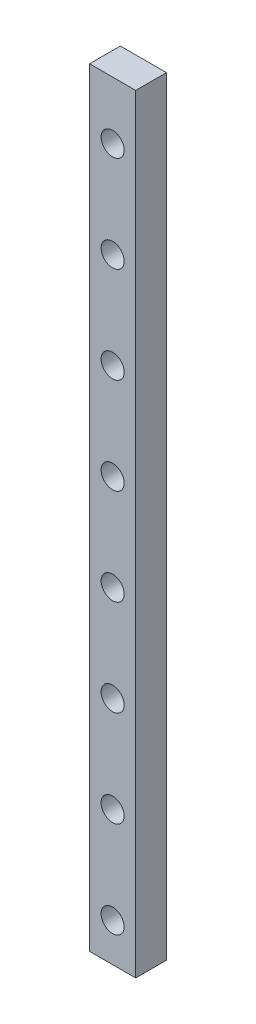
SolidWorks part; units mm, degrees
ref_plane "前视基准面" through (0, 0, 0) normal (0, 0, 1) x (1, 0, 0)
ref_plane "上视基准面" through (0, 0, 0) normal (0, 1, 0) x (1, 0, 0)
ref_plane "右视基准面" through (0, 0, 0) normal (1, 0, 0) x (0, 0, -1)
sketch "草图1" plane through (0, 0, 0) normal (0, 1, 0) x (1, 0, 0)
  line L1 (6, -4) -> (-6, -4)
  line L2 (6, -4) -> (6, 4)
  line L3 (6, 4) -> (-6, 4)
  line L4 (-6, -4) -> (-6, 4)
  line L5 (6, -4) -> (-6, 4) construction
  line L6 (6, 4) -> (-6, -4) construction
  point P0 (0, 0)
  dimension "D1" = 12
  dimension "D2" = 8
extrude "凸台-拉伸1" add sketch "草图1" along normal blind 200
sketch "草图2" plane through (0, 0, 4) normal (0, 0, 1) x (1, 0, 0)
  line L0 (0, -1000) -> (0, 49000) construction
  line L1 (-6, 0) -> (6, 0) construction
  circle A0 centre (0, 10) radius 3
  dimension "D1" = 6
  dimension "D2" = 10
extrude "切除-拉伸1" cut sketch "草图2" against normal blind 4.5
sketch "草图3" plane through (0, 0, -0.5) normal (0, 0, 1) x (1, 0, 0)
  circle A0 centre (0, 10) radius 1.75
  circle A1 centre (0, 10) radius 3
  circle A2 centre (0, 10) radius 3 construction
  dimension "D2" = 3.5
  dimension "D1" = 0
extrude "切除-拉伸2" cut sketch "草图3" against normal blind 4.5
pattern_linear "阵列(线性)1" count 8 spacing 25 along (0, 1, 0) of "切除-拉伸2", "切除-拉伸1"
